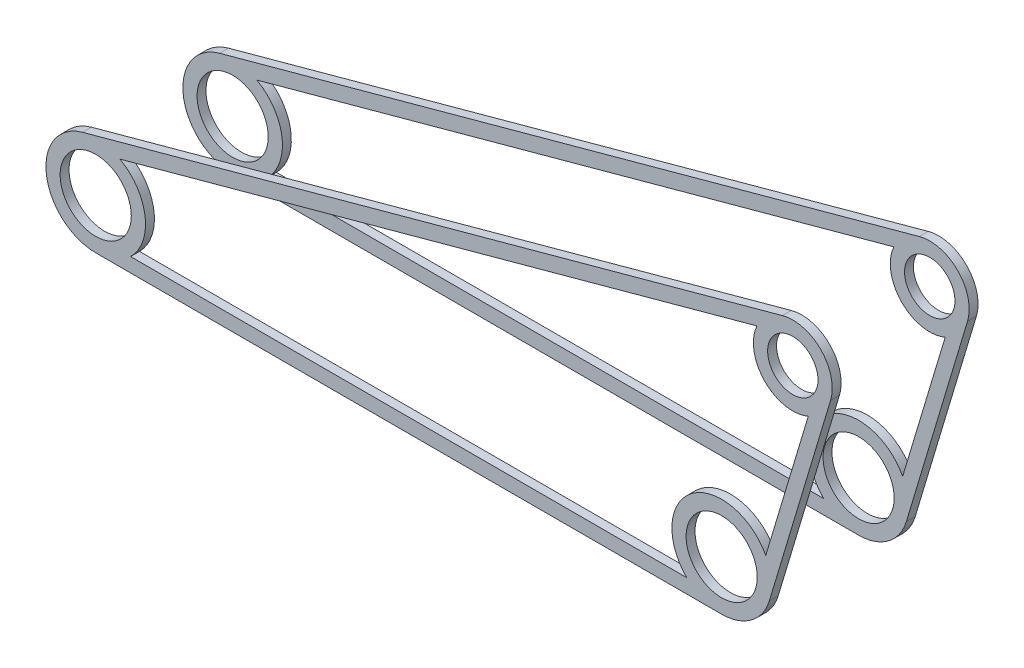
SolidWorks part; units mm, degrees
material "AISI 4130 Steel, annealed at 865C"
ref_plane "Front Plane" through (0, 0, 0) normal (0, 0, 1) x (1, 0, 0)
ref_plane "Top Plane" through (0, 0, 0) normal (0, 1, 0) x (1, 0, 0)
ref_plane "Right Plane" through (0, 0, 0) normal (1, 0, 0) x (0, 0, -1)
sketch "Sketch1" plane through (0, 0, 0) normal (0, 0, 1) x (1, 0, 0)
  line L0 (0, 0) -> (111.76, 0) construction
  line L1 (111.76, 0) -> (124.46, 35.921) construction
  line L2 (124.46, 35.921) -> (0, 0) construction
  line L3 (-2.3429, 8.5757) -> (122.6046, 42.7121)
  line L4 (131.2035, 33.8994) -> (120.2756, -2.5529)
  line L5 (111.76, -8.89) -> (0, -8.89)
  line L6 (-1.6735, 6.1255) -> (123.274, 40.2619)
  line L7 (0, -6.35) -> (111.76, -6.35)
  line L8 (117.8426, -1.8235) -> (128.7705, 34.6288)
  circle A0 centre (0, 0) radius 6.35
  circle A1 centre (111.76, 0) radius 6.35
  circle A2 centre (124.46, 35.921) radius 4.5
  circle A3 centre (0, 0) radius 8.89
  circle A4 centre (111.76, 0) radius 8.89
  circle A5 centre (124.46, 35.921) radius 7.04
  dimension "D1" = 9
  dimension "D2" = 12.7
  dimension "D3" = 12.7
  dimension "D6" = 2.54
  dimension "D7" = 2.54
  dimension "D8" = 2.54
  dimension "D4" = 111.76
  dimension "D5" = 129.54
  dimension "D9" = 38.1
extrude "Boss-Extrude1" add sketch "Sketch1" along normal blind 1.5875 from offset 11.43 contours A5 L3 A3 L6 | L6 A3 L7 A0 | A4 L7 A3 L5 | L7 A4 L8 A1 | A5 L8 A4 L4 | A5 L6 A2 L8 | L7 A3 L6 A0 | L8 A4 L7 A1 | L6 A5 L8 A2 region at (1.044, 8.5935, 0) region at (60.7098, 24.5019, 0) region at (128.6163, 41.3651, 0) region at (55.88, -7.64, 0) region at (7.5132, 4.4137, 0) region at (120.7051, 39.3935, 0) region at (108.4753, -8.0458, 0) region at (124.6564, 16.2601, 0) region at (106.5878, 6.9501, 0)
extrude "Boss-Extrude2" add sketch "Sketch1<4>" against normal blind 1.5875 from offset 11.43 separate body contours A5 L3 A3 L6 | L6 A3 L7 A0 | L7 A3 L6 A0 | A4 L7 A3 L5 | L7 A4 L8 A1 | L8 A4 L7 A1 | A5 L8 A4 L4 | L6 A5 L8 A2 | A5 L6 A2 L8 region at (1.044, 8.5935, 0) region at (60.7098, 24.5019, 0) region at (128.6163, 41.3651, 0) region at (55.88, -7.64, 0) region at (7.5132, 4.4137, 0) region at (120.7051, 39.3935, 0) region at (108.4753, -8.0458, 0) region at (124.6564, 16.2601, 0) region at (106.5878, 6.9501, 0) offset against normal yes
sketch "Sketch1<4>" plane through (0, 0, 0) normal (0, 0, 1) x (1, 0, 0) same geometry as "Sketch1"
equation "\"D19@Boss-Extrude2\"=.45"
